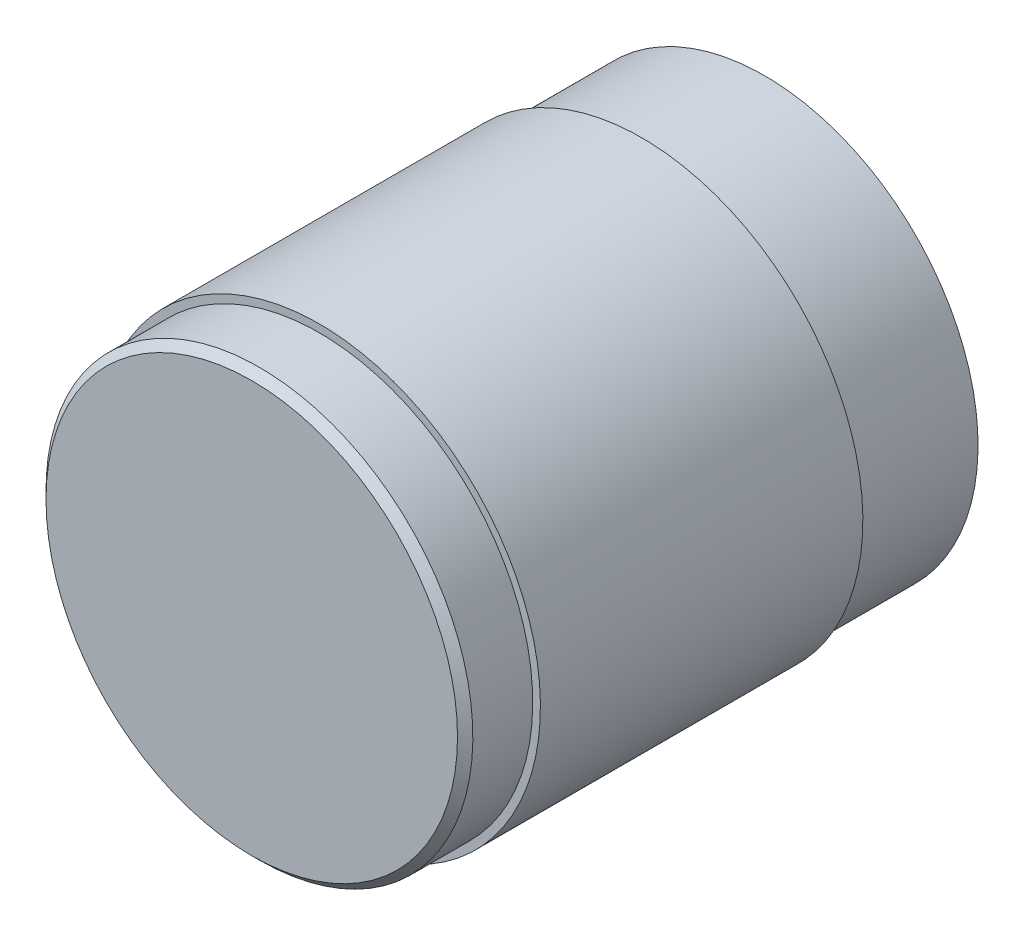
SolidWorks part; units mm, degrees
ref_plane "Front Plane" through (0, 0, 0) normal (1, 0, 0) x (0, 1, 0)
ref_plane "Top Plane" through (0, 0, 0) normal (0, 0, 1) x (0, 1, 0)
ref_plane "Right Plane" through (0, 0, 0) normal (0, 1, 0) x (-1, 0, 0)
sketch "Sketch2" plane through (0, 0, 21.4) normal (0, 0, 1) x (1, 0, 0)
  circle A0 centre (6.5601, 8.0018) radius 1.75 construction
  circle A1 centre (6.5601, 8.0018) radius 1.75 construction
  circle A2 centre (6.5601, 8.0018) radius 7.2
  circle A3 centre (6.5601, 8.0018) radius 6.95
  point P6 (0, 0)
  line M4 (5.0601, 10.2468) -> (5.0601, 5.7568)
  arc M5 (5.0601, 5.7568) -> (5.0601, 10.2468) centre (6.5601, 8.0018) ccw
  dimension "D1" = 14.4
  dimension "D2" = 13.9
extrude "Boss-Extrude1" add sketch "Sketch2" against normal blind 16.7 from offset 3.7 contours A3 M4 M5 | M5 M4 region at (-0.1934, 8.0018, 21.4) region at (6.9547, 8.0018, 21.4)
extrude "Boss-Extrude2" add sketch "Sketch2<4>" along normal blind 10.5 from offset 9 contours A2 A3 region at (-0.4363, 8.0018, 21.4) offset against normal yes
sketch "Sketch2<4>" plane through (0, 0, 21.4) normal (0, 0, 1) x (1, 0, 0) same geometry as "Sketch2"
chamfer "Chamfer1" distance 0.25 angle 45 1 edges at (6.5601, 1.0518, 25.1)
